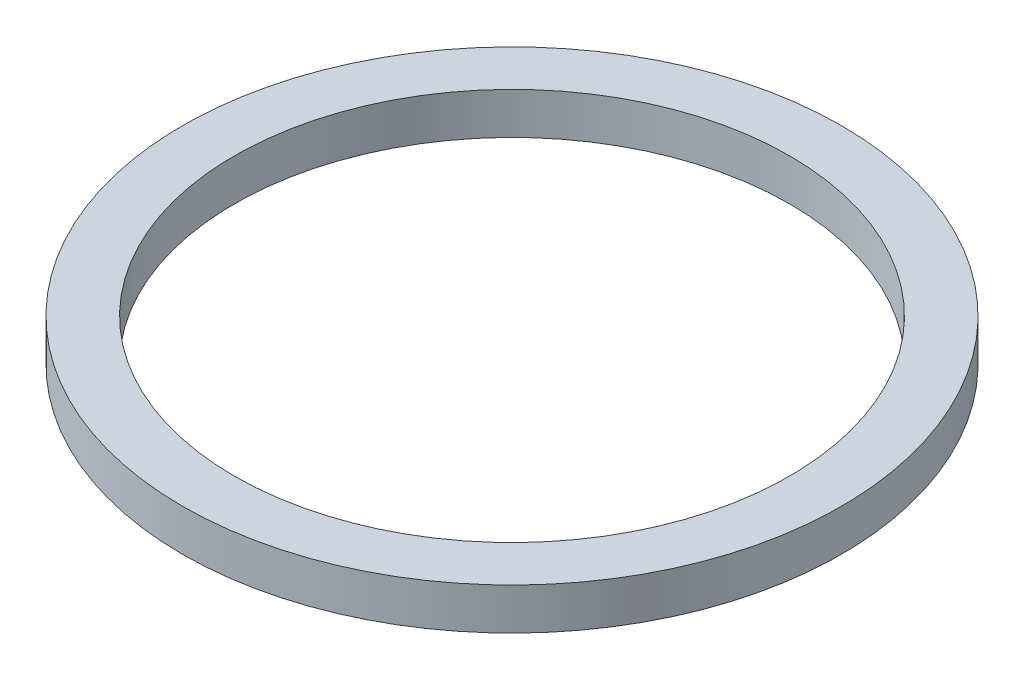
SolidWorks part; units mm, degrees
ref_plane "Front Plane" through (0, 0, 0) normal (0, 0, 1) x (1, 0, 0)
ref_plane "Top Plane" through (0, 0, 0) normal (0, 1, 0) x (1, 0, 0)
ref_plane "Right Plane" through (0, 0, 0) normal (1, 0, 0) x (0, 0, -1)
sketch "Sketch1" plane through (0, 0, 0) normal (0, 1, 0) x (1, 0, 0)
  circle A0 centre (0, 0) radius 47.5
  dimension "FLANGE_OD" = 95
extrude "Boss-Extrude1" add sketch "Sketch1" along normal blind 6
sketch "Sketch2" plane through (0, 0, 0) normal (0, 1, 0) x (1, 0, 0)
  circle A0 centre (0, 0) radius 40
  dimension "BORE_D" = 80
extrude "Cut-Extrude1" cut sketch "Sketch2" along normal through all
sketch "Sketch3" plane through (0, 6, 0) normal (0, 1, 0) x (1, 0, 0)
  circle A0 centre (0, 0) radius 21.9963 construction
  circle A1 centre (-21.9963, 0) radius 1.5
  dimension "BOLT_D" = 3
  dimension "BOLT_PCD" = 43.9926
extrude "Cut-Extrude2" cut sketch "Sketch3" against normal blind 5.5004 rebuild error yes
pattern_circular "CirPattern1" count 3 over 360 rebuild error yes
